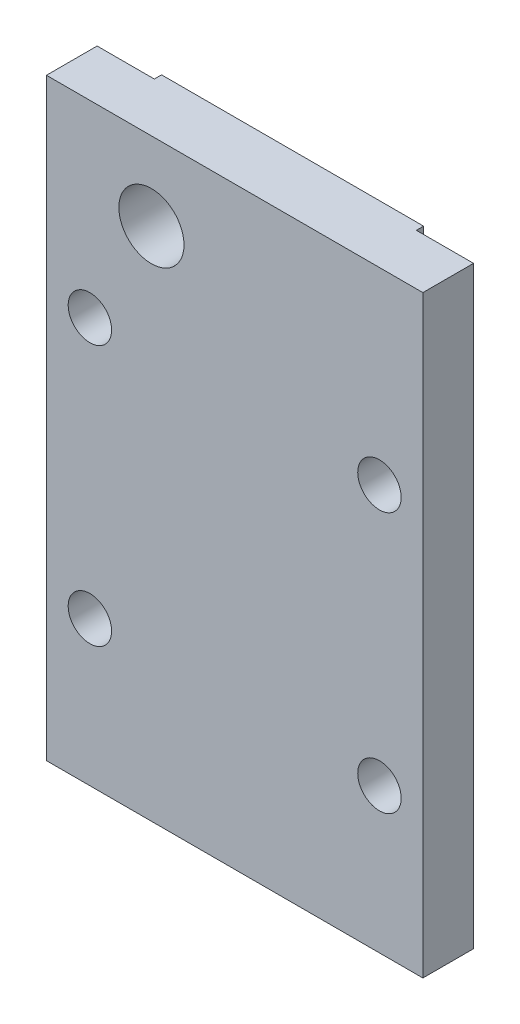
SolidWorks part; units mm, degrees
ref_plane "Front Plane" through (0, 0, 0) normal (0, 0, 1) x (1, 0, 0)
ref_plane "Top Plane" through (0, 0, 0) normal (0, 1, 0) x (1, 0, 0)
ref_plane "Right Plane" through (0, 0, 0) normal (1, 0, 0) x (0, 0, -1)
sketch "Sketch1" plane through (0, 0, 0) normal (0, 0, 1) x (1, 0, 0)
  line L8 (0, 0) -> (0, 41) construction
  line L9 (0, 41) -> (3.95, 41) construction
  line L10 (3.95, 41) -> (3.95, 31) construction
  line L11 (3.95, 31) -> (10.3, 31) construction
  line L12 (10.3, 31) -> (10.3, 9) construction
  line L13 (10.3, 9) -> (8.55, 9) construction
  line L14 (8.55, 9) -> (8.55, 4) construction
  line L15 (8.55, 4) -> (13, 4) construction
  line L16 (13, 4) -> (13, 0) construction
  line L17 (13, 0) -> (0, 0) construction
  line L18 (0, 0) -> (0, 41)
  line L19 (0, 41) -> (26, 41)
  line L20 (26, 41) -> (26, 0)
  line L21 (26, 0) -> (0, 0)
  line L22 (3, 41) -> (3, 0) construction
  line L23 (13, 41) -> (13, 0) construction
  circle A0 centre (7.25, 35.6) radius 2.25
  circle A1 centre (3, 28) radius 1.5
  circle A2 centre (3, 10) radius 1.5
  circle A3 centre (23, 10) radius 1.5
  circle A4 centre (23, 28) radius 1.5
  dimension "D12" = 4.5
  dimension "D11" = 5.75
  dimension "D13" = 3
  dimension "D15" = 10
  dimension "D1" = 10
  dimension "D2" = 41
  dimension "D3" = 4
  dimension "D4" = 10.3
  dimension "D5" = 13
  dimension "D6" = 9.05
  dimension "D7" = 5
  dimension "D8" = 1.75
  dimension "D9" = 26
  dimension "D10" = 5.4
  dimension "D14" = 3
  dimension "D16" = 13
extrude "Boss-Extrude1" add sketch "Sketch1" along normal blind 4
sketch "Sketch3" plane through (0, 0, 0) normal (0, 0, -1) x (-1, 0, 0)
  line L0 (-3.95, 41) -> (-22.05, 41)
  line L1 (-17.45, 9) -> (-17.45, 4)
  line L2 (-3.95, 41) -> (-3.95, 31)
  line L3 (-3.95, 31) -> (-10.3, 31)
  line L4 (-10.3, 28) -> (-10.3, 12)
  line L5 (-10.3, 9) -> (-8.55, 9)
  line L6 (-8.55, 9) -> (-8.55, 4)
  line L7 (-8.55, 4) -> (-17.45, 4)
  line L8 (-13, 41) -> (-13, 0) construction
  line L9 (-15.7, 9) -> (-17.45, 9)
  line L10 (-15.7, 28) -> (-15.7, 12)
  line L11 (-22.05, 31) -> (-15.7, 31)
  line L12 (-22.05, 41) -> (-22.05, 31)
  arc A0 (-10.3, 31) -> (-10.3, 28) centre (-10.3, 29.5) ccw
  arc A1 (-10.3, 9) -> (-10.3, 12) centre (-10.3, 10.5) cw
  arc A2 (-15.7, 9) -> (-15.7, 12) centre (-15.7, 10.5) ccw
  arc A3 (-15.7, 31) -> (-15.7, 28) centre (-15.7, 29.5) cw
  point P29 (-13, 4)
extrude "Cut-Extrude1" cut sketch "Sketch3" against normal blind 0.5 flip side to cut
